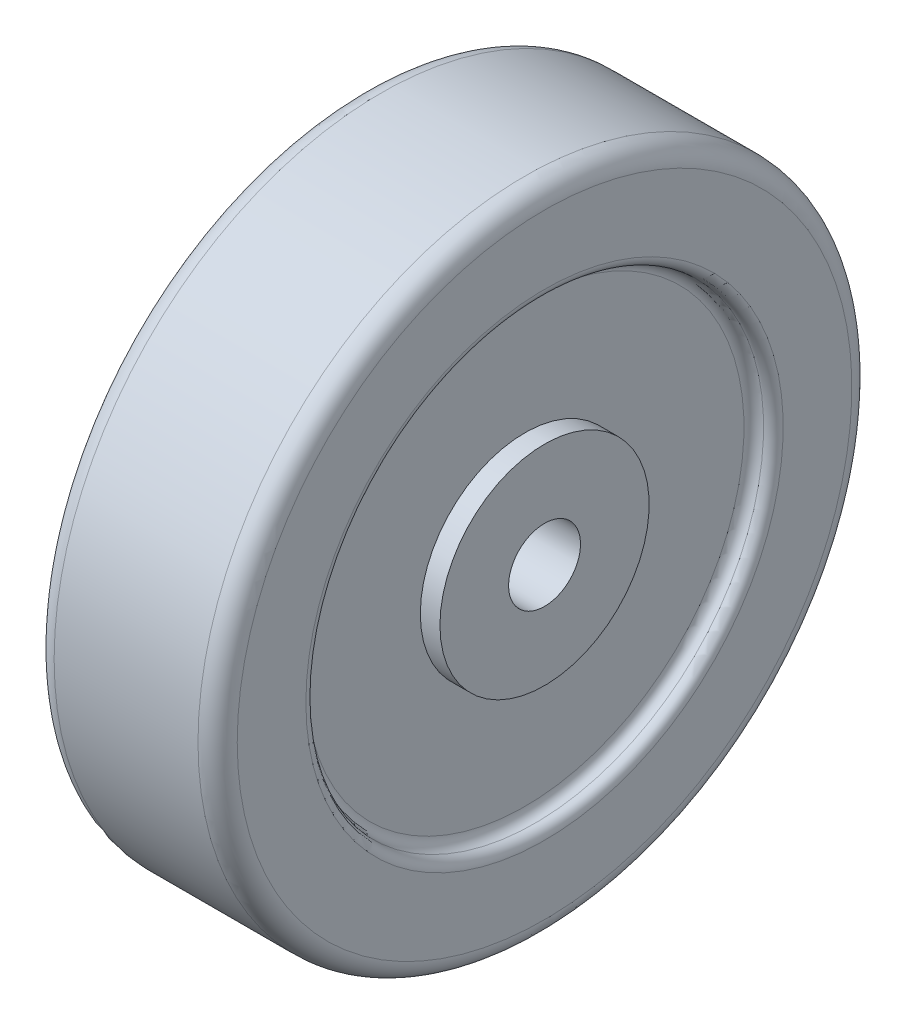
SolidWorks part; units mm, degrees
ref_plane "Front Plane" through (0, 0, 0) normal (0, 0, 1) x (1, 0, 0)
ref_plane "Top Plane" through (0, 0, 0) normal (0, 1, 0) x (1, 0, 0)
ref_plane "Right Plane" through (0, 0, 0) normal (1, 0, 0) x (0, 0, -1)
sketch "Sketch1" plane through (0, 0, 0) normal (0, 0, 1) x (1, 0, 0)
  line L0 (0, 0) -> (44.2119, 0) construction
  line L1 (0, 50) -> (28, 50)
  line L2 (28, 50) -> (28, 35)
  line L3 (28, 35) -> (25, 35)
  line L4 (25, 35) -> (25, 16)
  line L5 (25, 16) -> (28, 16)
  line L6 (28, 16) -> (28, 5.5)
  line L7 (28, 5.5) -> (0, 5.5)
  line L8 (0, 5.5) -> (0, 16)
  line L9 (0, 16) -> (3, 16)
  line L10 (3, 16) -> (3, 35)
  line L11 (3, 35) -> (0, 35)
  line L12 (0, 35) -> (0, 50)
  dimension "D1" = 28
  dimension "D2" = 50
  dimension "D3" = 35
  dimension "D4" = 16
  dimension "D5" = 3
  dimension "D6" = 5.5
revolve "Revolve1" add sketch "Sketch1" angle 360 about L0 other way angle 360
fillet "Fillet1" radius 3 2 edges at (0, 0, 50) (28, 0, 50)
fillet "Fillet2" radius 1.5 4 edges at (0, 0, 35) (3, 0, 35) (28, 0, 35) (25, 0, 35)
